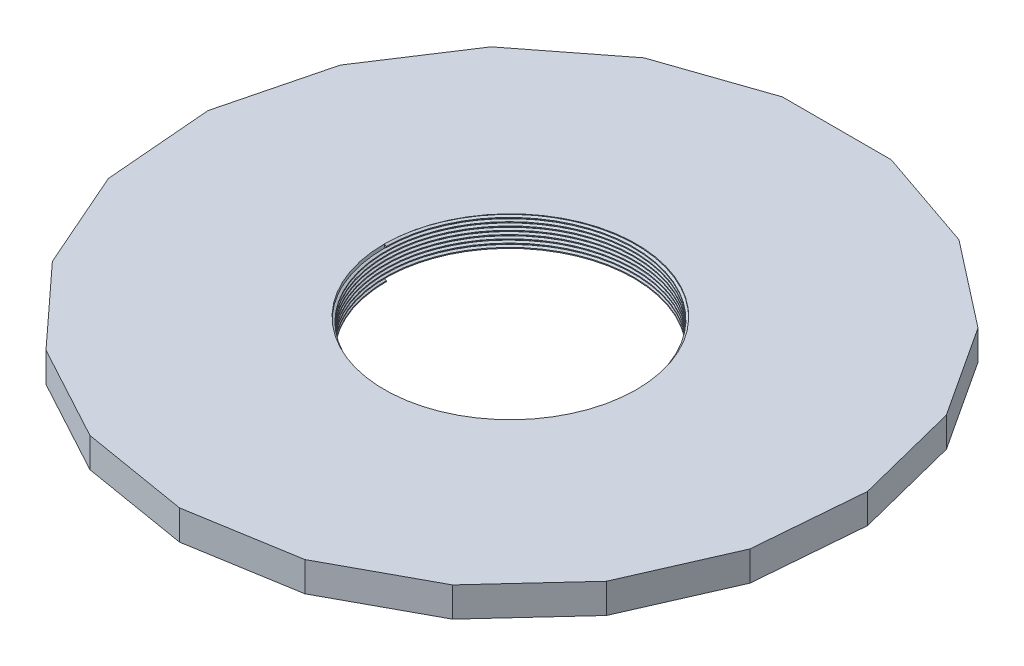
SolidWorks part; units mm, degrees
ref_plane "Front Plane" through (0, 0, 0) normal (0, 0, 1) x (1, 0, 0)
ref_plane "Top Plane" through (0, 0, 0) normal (0, 1, 0) x (1, 0, 0)
ref_plane "Right Plane" through (0, 0, 0) normal (1, 0, 0) x (0, 0, -1)
sketch "Sketch10" plane through (0, 0, 0) normal (0, 1, 0) x (1, 0, 0)
  line L0 (-21.6217, -5.4754) -> (-18.6723, -12.1992)
  line L1 (3.6712, 22) -> (-3.6712, 22)
  line L2 (-3.6712, 22) -> (-10.6156, 19.616)
  line L3 (-10.6156, 19.616) -> (-16.4097, 15.1062)
  line L4 (-16.4097, 15.1062) -> (-20.4256, 8.9595)
  line L5 (-20.4256, 8.9595) -> (-22.228, 1.8419)
  line L6 (-22.228, 1.8419) -> (-21.6217, -5.4754)
  line L7 (-18.6723, -12.1992) -> (-13.6995, -17.6011)
  line L8 (-13.6995, -17.6011) -> (-7.2422, -21.0957)
  line L9 (-7.2422, -21.0957) -> (0, -22.3042)
  line L10 (0, -22.3042) -> (7.2422, -21.0957)
  line L11 (7.2422, -21.0957) -> (13.6995, -17.6011)
  line L12 (13.6995, -17.6011) -> (18.6723, -12.1992)
  line L13 (18.6723, -12.1992) -> (21.6217, -5.4754)
  line L14 (21.6217, -5.4754) -> (22.228, 1.8419)
  line L15 (22.228, 1.8419) -> (20.4256, 8.9595)
  line L16 (20.4256, 8.9595) -> (16.4097, 15.1062)
  line L17 (16.4097, 15.1062) -> (10.6156, 19.616)
  line L18 (10.6156, 19.616) -> (3.6712, 22)
  circle A0 centre (0, 0) radius 22 construction
  circle A1 centre (0, 0) radius 22 construction
  point P22 (0, 22)
  dimension "D1" = 44
extrude "Boss-Extrude4" add sketch "Sketch10" along normal blind 2
sketch "Sketch14" plane through (0, 2, 0) normal (0, 1, 0) x (1, 0, 0)
  circle A0 centre (0, 0) radius 8.5
  dimension "D1" = 17
extrude "Cut-Extrude3" cut sketch "Sketch14" against normal through all
thread "Thread4" pitch 0.25 method extrude profile "Thread Profile4" start angle 0, offset 0, length 0, pitch 0.25, diameter 17
ref_plane "Plane4" through (-8.5, 2, 0) normal (0, 0, 1) x (-1, 0, 0)
sketch "Thread Profile4" plane through (-8.5, 2, 0) normal (0, 0, 1) x (-1, 0, 0)
  line L0 (0, 0) -> (0, 0.25) construction
  line L11 (0, 0) -> (0, 0.2187)
  line L12 (0, 0.2187) -> (-0.1353, 0.1406)
  line L13 (-0.1353, 0.1406) -> (-0.1353, 0.0781)
  line L15 (-0.1353, 0.0781) -> (0, 0)
  line L17 (-0.1353, 0.1094) -> (0, 0.1094) construction
  point P2 (0, 0)
  dimension "Pitch" = 0.25
  dimension "Profile_Angle" = 60
  dimension "Profile_Land" = 0.0625
  dimension "Profile_Height" = 0.1353
equation "\"diameter_ring_outer\"= 60mm"
equation "\"height_ring\"= 15mm"
equation "\"dist_tube_bottom\"= 1mm"
equation "\"diameter_ring_inner\"= 40mm"
equation "\"length_spring_expand\"= 15mm"
equation "\"length_spring_compress\"= 7.5mm"
equation "\"height_slit\"= 5mm"
equation "\"diameter_spring_inner\"= 3.5mm"
equation "\"length_slit_inner\"= 1.5mm"
equation "\"num_electrodes\"= 19"
equation "\"diameter_screw_Cz\"= 13mm"
equation "\"dist_spring_center\"= 7mm"
equation "\"height_thread\"= 2mm"
equation "\"width_wall\"= 1mm"
equation "\"diameter_tube\"= 2mm"
equation "\"length_stop\"= 1mm"
equation "\"height_stop\"= 1mm"
equation "\"indent_thread\"= 1mm"
equation "\"diameter_connect_bottom\"= \"diameter_ring_outer\" - 5mm"
equation "\"width_connect_bottom\"= 2mm"
equation "\"offset\"= 0.5mm"
equation "\"D1@Sketch10\"=\"diameter_ring_inner\"+\"width_wall\"*4"
equation "\"height_cap\"= 2mm"
equation "\"D1@Boss-Extrude4\"=\"height_cap\""
equation "\"D1@Sketch14\"=\"diameter_screw_Cz\"+\"width_wall\"*4"
